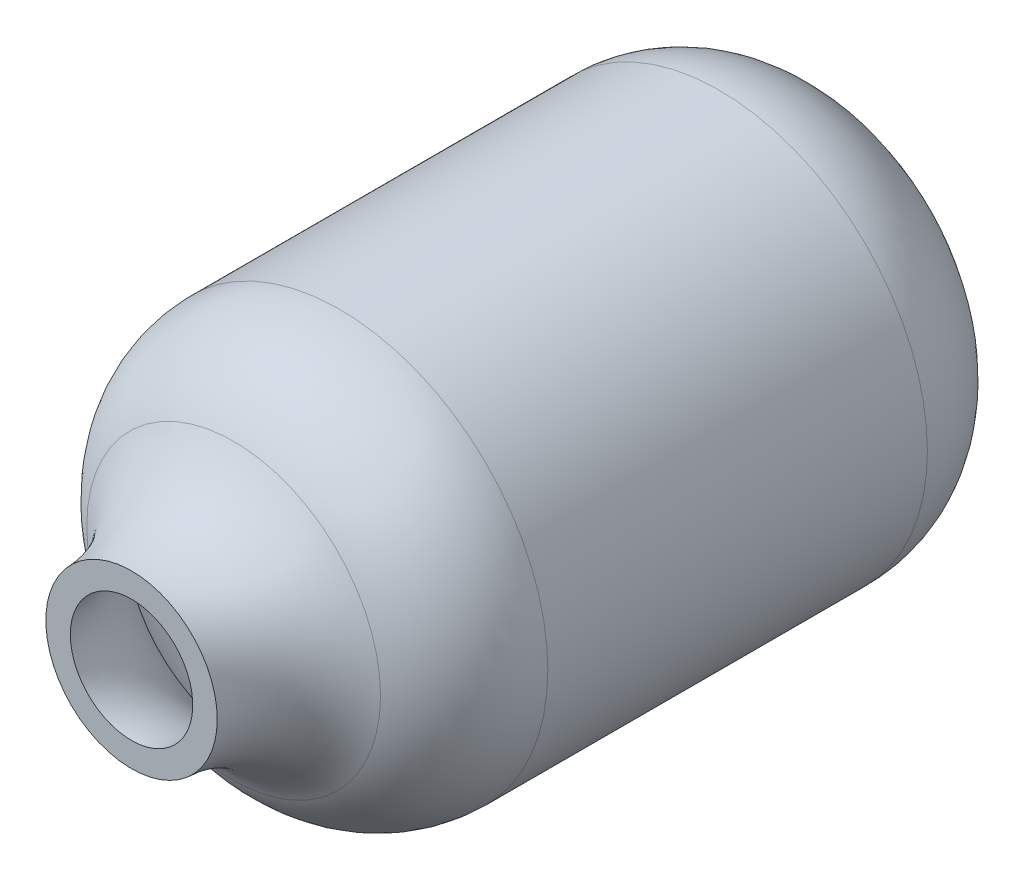
SolidWorks part; units mm, degrees
ref_plane "Front Plane" through (0, 0, 0) normal (0, 0, 1) x (1, 0, 0)
ref_plane "Top Plane" through (0, 0, 0) normal (0, 1, 0) x (1, 0, 0)
ref_plane "Right Plane" through (0, 0, 0) normal (1, 0, 0) x (0, 0, -1)
sketch "Sketch1" plane through (0, 0, 0) normal (0, 0, 1) x (1, 0, 0)
  circle A0 centre (0, 0) radius 17
  dimension "D1" = 34
extrude "Boss-Extrude1" add sketch "Sketch1" along normal blind 51
fillet "Fillet1" radius 10 1 edges at (17, 0, 0)
fillet "Fillet2" radius 10 1 edges at (17, 0, 51)
sketch "Sketch2" plane through (0, 0, 51) normal (0, 0, 1) x (1, 0, 0)
  circle A1 centre (0, 0) radius 7
  circle A2 centre (0, 0) radius 7
  dimension "D1" = 0
extrude "Boss-Extrude2" add sketch "Sketch2" along normal blind 7
fillet "Fillet3" radius 10 1 edges at (7, 0, 51)
shell "Shell1" thickness 2 removed face at (7, 0, 58)
